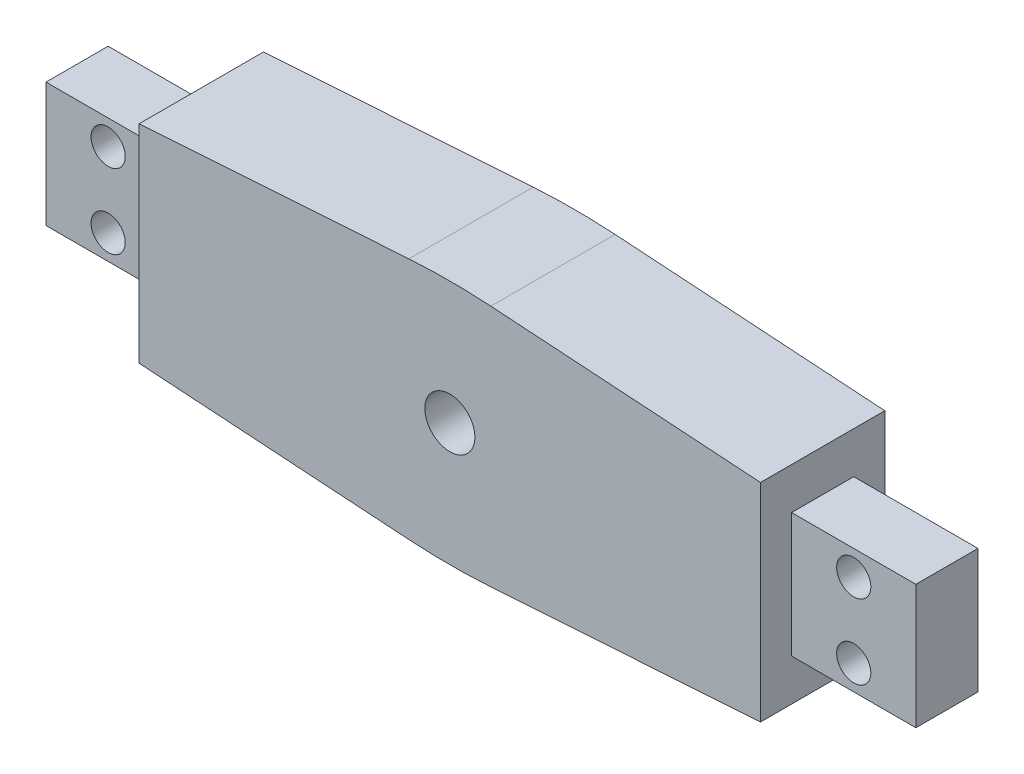
SolidWorks part; units mm, degrees
ref_plane "Front Plane" through (0, 0, 0) normal (0, 0, 1) x (1, 0, 0)
ref_plane "Top Plane" through (0, 0, 0) normal (0, 1, 0) x (1, 0, 0)
ref_plane "Right Plane" through (0, 0, 0) normal (1, 0, 0) x (0, 0, -1)
sketch "Sketch1" plane through (0, 0, 0) normal (0, 0, 1) x (1, 0, 0)
  line L0 (0, 0) -> (-50000, 0) construction
  line L1 (0, -20) -> (151.3167, -10) construction
  line L2 (0, 20) -> (151.3167, 10) construction
  line L3 (0, 0) -> (0, 50000) construction
  line L4 (122.4484, -204.4828) -> (119.5098, 130.5043) construction
  line L5 (0, -20) -> (-151.3167, -10) construction
  line L6 (0, 20) -> (-151.3167, 10) construction
  line L7 (50, 16.6957) -> (50, -16.6957)
  line L8 (50, 16.6957) -> (0, 20)
  line L9 (0, -20) -> (50, -16.6957)
  line L10 (0, -20) -> (-50, -16.6957)
  line L11 (-50, 16.6957) -> (-50, -16.6957)
  line L12 (-50, 16.6957) -> (0, 20)
  circle A1 centre (0, 0) radius 4.025
  arc A2 (-151.3167, -10) -> (-151.3167, 10) centre (-150.6558, 0) ccw construction
  arc A3 (151.3167, -10) -> (151.3167, 10) centre (150.6558, 0) cw construction
  dimension "D1" = 40
  dimension "D2" = 8.05
  dimension "D3" = 20
  dimension "D4" = 30
  dimension "D5" = 50
extrude "Boss-Extrude1" add sketch "Sketch1" along normal blind 20
fillet "Fillet1" radius 100 2 edges at (0, 20, 10) (0, -20, 10)
sketch "Sketch2" plane through (50, 0, 0) normal (1, 0, 0) x (0, 0, -1)
  line L1 (-15, 10) -> (-5, 10)
  line L2 (-15, 10) -> (-15, -10)
  line L3 (-15, -10) -> (-5, -10)
  line L4 (0, -16.6957) -> (0, 16.6957)
  line L5 (-20, -16.6957) -> (0, -16.6957)
  line L6 (-20, 16.6957) -> (-20, -16.6957)
  line L7 (0, 16.6957) -> (-20, 16.6957)
  line L8 (0, -16.6957) -> (0, 16.6957)
  line L9 (-20, -16.6957) -> (0, -16.6957)
  line L10 (-20, 16.6957) -> (-20, -16.6957)
  line L11 (0, 16.6957) -> (-20, 16.6957)
  line L12 (-5, 10) -> (-5, -10)
  line L13 (-15, 10) -> (-5, -10) construction
  line L14 (-15, -10) -> (-5, 10) construction
  point P2 (-10, 0)
  point P10 (-10, -16.6957)
  dimension "D2" = 10
  dimension "D3" = 20
  dimension "D1" = 0
extrude "Boss-Extrude2" add sketch "Sketch2" along normal blind 20 contours L12 L1 L2 L3 region at (50, 0, 10)
mirror "Mirror1" about plane through (0, 0, 0) normal (1, 0, 0) of "Boss-Extrude2"
sketch "Sketch3" plane through (0, 0, 5) normal (0, 0, -1) x (-1, 0, 0)
  circle A0 centre (60, -6) radius 2.75 construction
  circle A1 centre (60, 6) radius 2.75 construction
  circle A2 centre (-60, -6) radius 2.75 construction
  circle A3 centre (-60, 6) radius 2.75 construction
  circle A4 centre (60, -6) radius 2.75
  circle A5 centre (60, 6) radius 2.75
  circle A6 centre (-60, -6) radius 2.75
  circle A7 centre (-60, 6) radius 2.75
extrude "Cut-Extrude1" cut sketch "Sketch3" against normal through all
